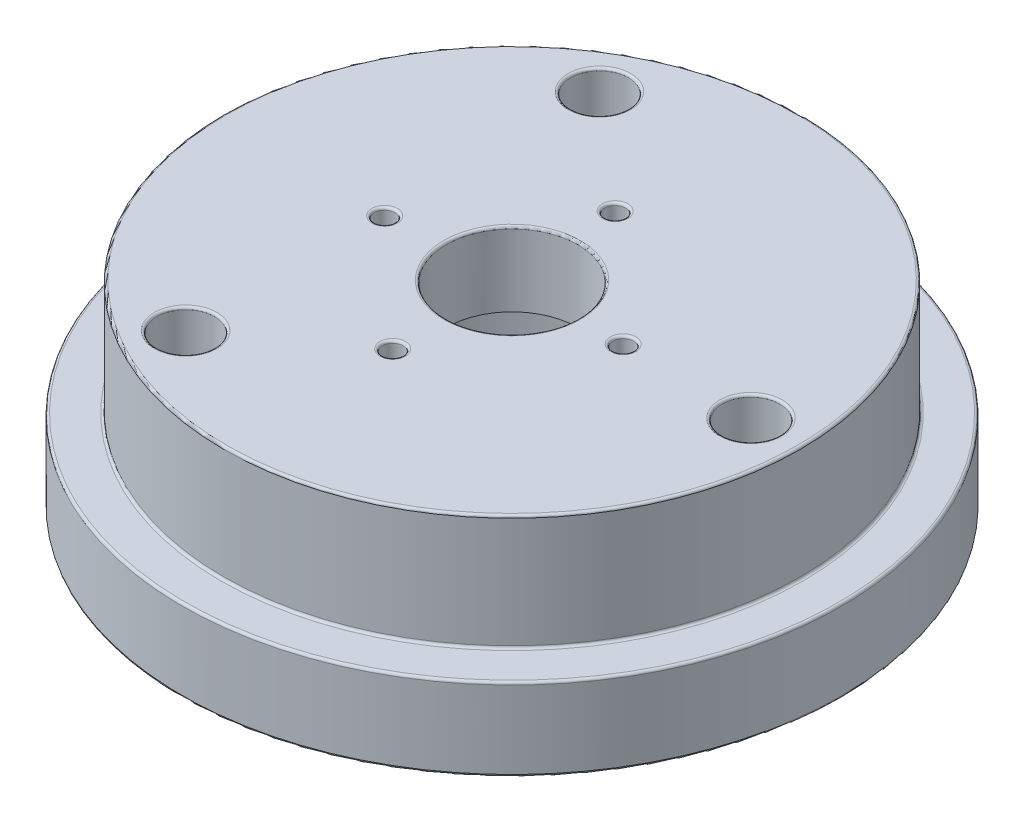
SolidWorks part; units mm, degrees
ref_plane "Front Plane" through (0, 0, 0) normal (0, 0, 1) x (1, 0, 0)
ref_plane "Top Plane" through (0, 0, 0) normal (0, 1, 0) x (1, 0, 0)
ref_plane "Right Plane" through (0, 0, 0) normal (1, 0, 0) x (0, 0, -1)
sketch "Sketch1" plane through (0, 0, 0) normal (0, 0, 1) x (1, 0, 0)
  line L0 (0, 0) -> (-20, 0)
  line L1 (-20, 0) -> (-20, 5)
  line L2 (-20, 5) -> (-17.5, 5)
  line L3 (-17.5, 5) -> (-17.5, 12)
  line L4 (-17.5, 12) -> (0, 12)
  line L5 (0, 12) -> (0, 0)
  dimension "D1" = 12
  dimension "D2" = 5
  dimension "D3" = 20
  dimension "D4" = 17.5
revolve "Revolve1" add sketch "Sketch1" angle 360 about L5
sketch "Sketch2" plane through (0, 0, 0) normal (0, -1, 0) x (1, 0, 0)
  circle A0 centre (0, 0) radius 10
  circle A1 centre (14.5, 0) radius 1.75
  circle A2 centre (-7.25, -12.5574) radius 1.75
  circle A3 centre (-7.25, 12.5574) radius 1.75
  circle A4 centre (0, 0) radius 20 construction
  circle A5 centre (0, 0) radius 4
  circle A6 centre (6.75, 0) radius 0.625
  circle A7 centre (-0.4914, -6.75) radius 0.625
  circle A8 centre (-7.2414, 0.4914) radius 0.625
  circle A9 centre (0, 7.2414) radius 0.625
  point P12 (0, 0)
  point P24 (-0.2457, 0.2457)
  dimension "D1" = 3.5
  dimension "D2" = 20
  dimension "D5" = 8
  dimension "D6" = 1.25
  dimension "D3" = 14.5
  dimension "D7" = 6.75
  dimension "D4" = 3
  dimension "D8" = 4
extrude "Cut-Extrude2" cut sketch "Sketch2" against normal through all contours A3 | A8 | A7 | A1 | A5 | A2 | A6 | A9 region at (14.5, 0, 0) region at (-7.25, 0, -12.5574) region at (-7.25, 0, 12.5574) region at (0, 0, 0) region at (-0.4914, 0, -6.75) region at (-7.2414, 0, 0.4914)
extrude "Cut-Extrude3" cut sketch "Sketch2<4>" against normal blind 7.5
sketch "Sketch2<4>" plane through (0, 0, 0) normal (0, -1, 0) x (1, 0, 0) same geometry as "Sketch2"
fillet "Fillet1" radius 0.15 16 edges at (-17.5, 5, 0) (-20, 5, 0) (-17.5, 12, 0) (-7.25, 12, 10.8074) (-7.2414, 12, -0.1336) (-0.4914, 12, -7.375) (14.5, 12, -1.75) (0, 12, -4) (-7.25, 12, -14.3074) (6.75, 12, -0.625) (0, 12, 6.6164) (-20, 0, 0) (-7.25, 0, 10.8074) (14.5, 0, -1.75) (-7.25, 0, -14.3074) (0, 0, -10)
